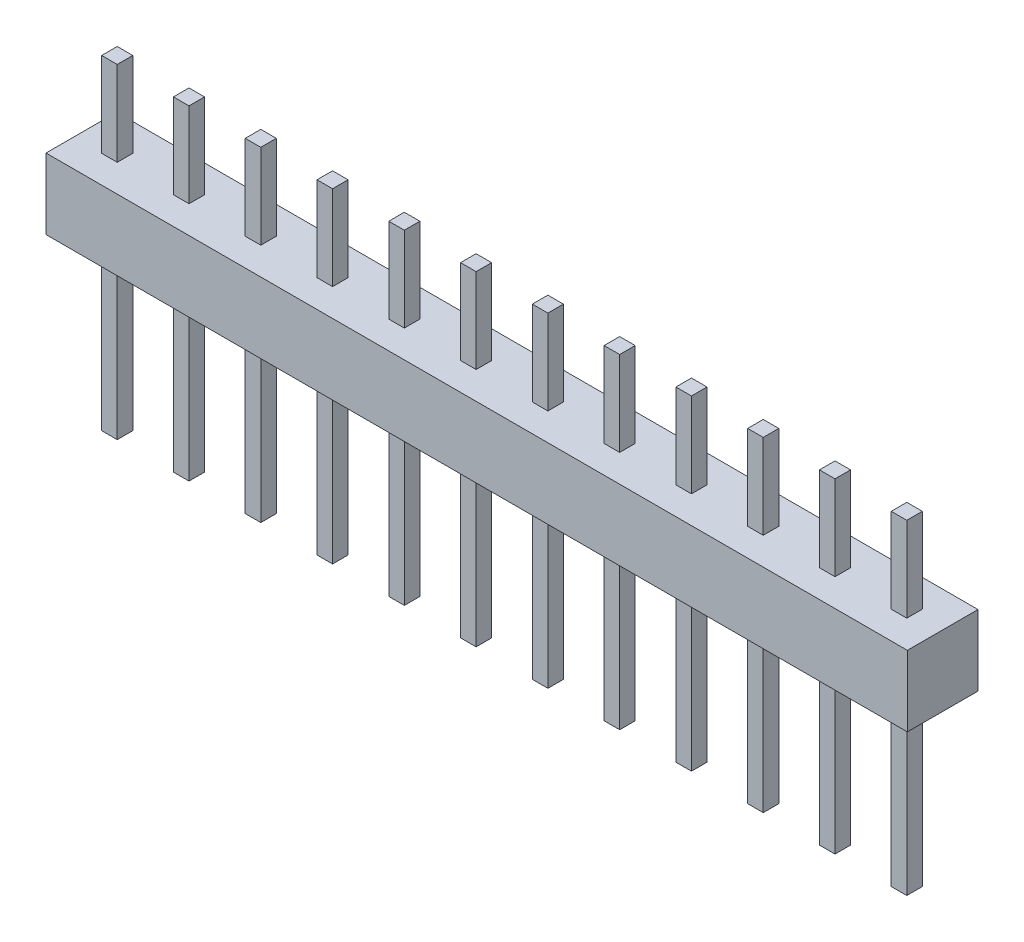
SolidWorks part; units mm, degrees
ref_plane "Front Plane" through (0, 0, 0) normal (0, 0, 1) x (1, 0, 0)
ref_plane "Top Plane" through (0, 0, 0) normal (0, 1, 0) x (1, 0, 0)
ref_plane "Right Plane" through (0, 0, 0) normal (1, 0, 0) x (0, 0, -1)
sketch "Sketch1" plane through (0, 0, 0) normal (0, 0, 1) x (1, 0, 0)
  line L1 (0, 0) -> (30.48, 0)
  line L2 (0, 0) -> (0, 2.5)
  line L3 (0, 2.5) -> (30.48, 2.5)
  line L4 (30.48, 0) -> (30.48, 2.5)
  dimension "D1" = 2.5
  dimension "D2" = 30.48
extrude "Boss-Extrude1" add sketch "Sketch1" along normal mid plane 2.5
sketch "Sketch2" plane through (0, 0, 0) normal (0, -1, 0) x (1, 0, 0)
  line L0 (0, 0) -> (30.48, 0) construction
  line L1 (30.48, 1.25) -> (30.48, -1.25) construction
  line L2 (3.535, -0.275) -> (4.085, -0.275)
  line L3 (0.995, -0.275) -> (1.545, -0.275)
  line L4 (0.995, -0.275) -> (0.995, 0.275)
  line L5 (0.995, 0.275) -> (1.545, 0.275)
  line L6 (1.545, -0.275) -> (1.545, 0.275)
  line L7 (0.995, -0.275) -> (1.545, 0.275) construction
  line L8 (0.995, 0.275) -> (1.545, -0.275) construction
  line L9 (3.535, -0.275) -> (3.535, 0.275)
  line L10 (3.535, 0.275) -> (4.085, 0.275)
  line L11 (4.085, -0.275) -> (4.085, 0.275)
  line L12 (3.535, -0.275) -> (4.085, 0.275) construction
  line L13 (3.535, 0.275) -> (4.085, -0.275) construction
  line L14 (1.27, 0) -> (3.81, 0) construction
  line L15 (6.075, -0.275) -> (6.625, -0.275)
  line L16 (6.075, -0.275) -> (6.075, 0.275)
  line L17 (6.075, 0.275) -> (6.625, 0.275)
  line L18 (6.625, -0.275) -> (6.625, 0.275)
  line L19 (6.075, -0.275) -> (6.625, 0.275) construction
  line L20 (6.075, 0.275) -> (6.625, -0.275) construction
  line L21 (8.615, -0.275) -> (9.165, -0.275)
  line L22 (8.615, -0.275) -> (8.615, 0.275)
  line L23 (8.615, 0.275) -> (9.165, 0.275)
  line L24 (9.165, -0.275) -> (9.165, 0.275)
  line L25 (8.615, -0.275) -> (9.165, 0.275) construction
  line L26 (8.615, 0.275) -> (9.165, -0.275) construction
  line L27 (11.155, -0.275) -> (11.705, -0.275)
  line L28 (11.155, -0.275) -> (11.155, 0.275)
  line L29 (11.155, 0.275) -> (11.705, 0.275)
  line L30 (11.705, -0.275) -> (11.705, 0.275)
  line L31 (11.155, -0.275) -> (11.705, 0.275) construction
  line L32 (11.155, 0.275) -> (11.705, -0.275) construction
  line L33 (13.695, -0.275) -> (14.245, -0.275)
  line L34 (13.695, -0.275) -> (13.695, 0.275)
  line L35 (13.695, 0.275) -> (14.245, 0.275)
  line L36 (14.245, -0.275) -> (14.245, 0.275)
  line L37 (13.695, -0.275) -> (14.245, 0.275) construction
  line L38 (13.695, 0.275) -> (14.245, -0.275) construction
  line L39 (16.235, -0.275) -> (16.785, -0.275)
  line L40 (16.235, -0.275) -> (16.235, 0.275)
  line L41 (16.235, 0.275) -> (16.785, 0.275)
  line L42 (16.785, -0.275) -> (16.785, 0.275)
  line L43 (16.235, -0.275) -> (16.785, 0.275) construction
  line L44 (16.235, 0.275) -> (16.785, -0.275) construction
  line L45 (18.775, -0.275) -> (19.325, -0.275)
  line L46 (18.775, -0.275) -> (18.775, 0.275)
  line L47 (18.775, 0.275) -> (19.325, 0.275)
  line L48 (19.325, -0.275) -> (19.325, 0.275)
  line L49 (18.775, -0.275) -> (19.325, 0.275) construction
  line L50 (18.775, 0.275) -> (19.325, -0.275) construction
  line L51 (21.315, -0.275) -> (21.865, -0.275)
  line L52 (21.315, -0.275) -> (21.315, 0.275)
  line L53 (21.315, 0.275) -> (21.865, 0.275)
  line L54 (21.865, -0.275) -> (21.865, 0.275)
  line L55 (21.315, -0.275) -> (21.865, 0.275) construction
  line L56 (21.315, 0.275) -> (21.865, -0.275) construction
  line L57 (23.855, -0.275) -> (24.405, -0.275)
  line L58 (23.855, -0.275) -> (23.855, 0.275)
  line L59 (23.855, 0.275) -> (24.405, 0.275)
  line L60 (24.405, -0.275) -> (24.405, 0.275)
  line L61 (23.855, -0.275) -> (24.405, 0.275) construction
  line L62 (23.855, 0.275) -> (24.405, -0.275) construction
  line L63 (26.395, -0.275) -> (26.945, -0.275)
  line L64 (26.395, -0.275) -> (26.395, 0.275)
  line L65 (26.395, 0.275) -> (26.945, 0.275)
  line L66 (26.945, -0.275) -> (26.945, 0.275)
  line L67 (26.395, -0.275) -> (26.945, 0.275) construction
  line L68 (26.395, 0.275) -> (26.945, -0.275) construction
  line L69 (28.935, -0.275) -> (29.485, -0.275)
  line L70 (28.935, -0.275) -> (28.935, 0.275)
  line L71 (28.935, 0.275) -> (29.485, 0.275)
  line L72 (29.485, -0.275) -> (29.485, 0.275)
  line L73 (28.935, -0.275) -> (29.485, 0.275) construction
  line L74 (28.935, 0.275) -> (29.485, -0.275) construction
  point P5 (1.27, 0)
  point P12 (3.81, 0)
  point P18 (6.35, 0)
  point P23 (8.89, 0)
  point P28 (11.43, 0)
  point P33 (13.97, 0)
  point P38 (16.51, 0)
  point P43 (19.05, 0)
  point P48 (21.59, 0)
  point P53 (24.13, 0)
  point P58 (26.67, 0)
  point P63 (29.21, 0)
  dimension "D1" = 0.55
  dimension "D3" = 1.27
  dimension "D4" = 2.54
  dimension "D2" = 12
extrude "Boss-Extrude2" add sketch "Sketch2" along normal blind 6 separate body
ref_axis "Axis1" through (1.27, 0, 0) along (0, -1, 0)
ref_axis "Axis2" through (29.21, 0, 0) along (0, -1, 0)
extrude "Boss-Extrude3" add sketch "Sketch2<2>" against normal blind 5.5 separate body
sketch "Sketch2<2>" plane through (0, 0, 0) normal (0, -1, 0) x (1, 0, 0) same geometry as "Sketch2"
